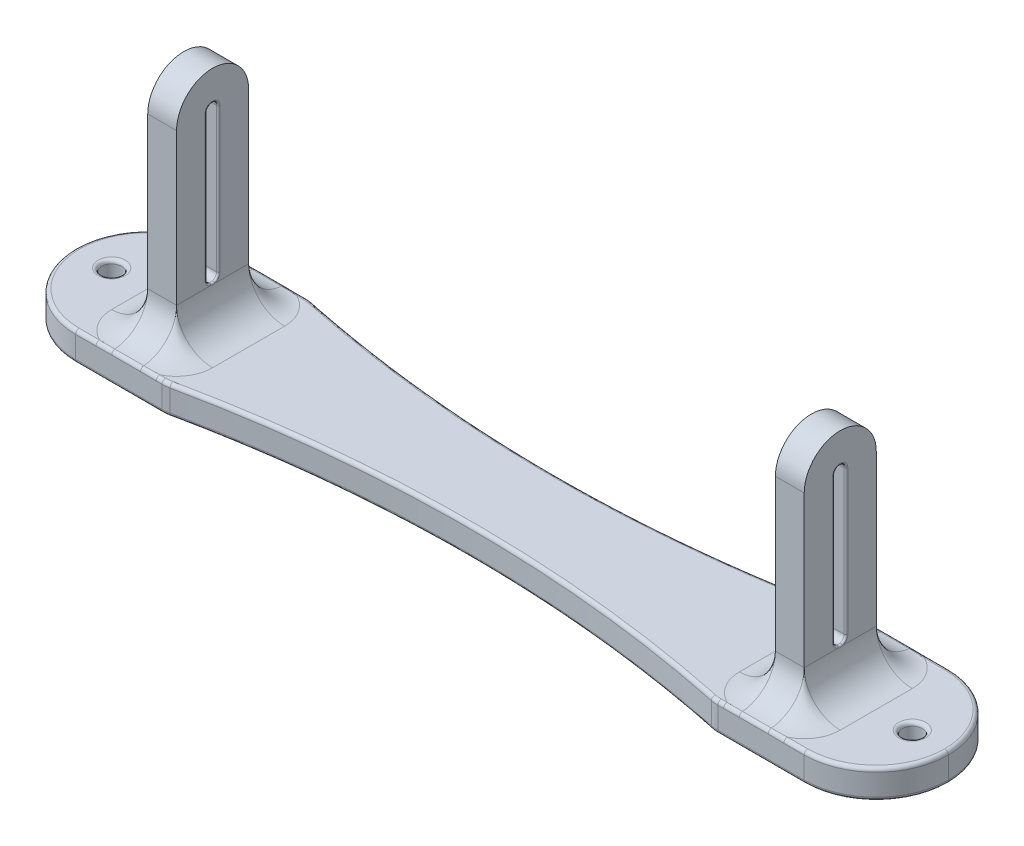
SolidWorks part; units mm, degrees
ref_plane "Front Plane" through (0, 0, 0) normal (0, 0, 1) x (1, 0, 0)
ref_plane "Top Plane" through (0, 0, 0) normal (0, 1, 0) x (1, 0, 0)
ref_plane "Right Plane" through (0, 0, 0) normal (1, 0, 0) x (0, 0, -1)
sketch "Sketch1" plane through (0, 0, 0) normal (0, 0, 1) x (1, 0, 0)
  line L1 (-91.1, 8) -> (-91.1, 70)
  line L2 (-91.1, 70) -> (-83.1, 70)
  line L3 (-83.1, 70) -> (-83.1, 8)
  line L5 (0, 0) -> (0, 8) construction
  line L10 (-121.1, 0) -> (-121.1, 8)
  line L11 (-121.1, 8) -> (-91.1, 8)
  line L12 (121.1, 0) -> (-121.1, 0)
  line L13 (83.1, 8) -> (-83.1, 8)
  line L14 (121.1, 8) -> (91.1, 8)
  line L15 (121.1, 0) -> (121.1, 8)
  line L16 (83.1, 70) -> (83.1, 8)
  line L17 (91.1, 70) -> (83.1, 70)
  line L18 (91.1, 8) -> (91.1, 70)
  dimension "D1" = 166.2
  dimension "D2" = 8
  dimension "D3" = 8
  dimension "D4" = 30
  dimension "D5" = 70
extrude "Boss-Extrude1" add sketch "Sketch1" along normal blind 40
sketch "Sketch2" plane through (91.1, 0, 0) normal (1, 0, 0) x (0, 0, -1)
  line L0 (-20, 60) -> (-20, 20) construction
  line L1 (-18.4, 60) -> (-18.4, 20)
  line L2 (-21.6, 60) -> (-21.6, 20)
  line L3 (-40, 70) -> (0, 70) construction
  arc A0 (-18.4, 60) -> (-21.6, 60) centre (-20, 60) ccw
  arc A1 (-21.6, 20) -> (-18.4, 20) centre (-20, 20) ccw
  point P2 (-20, 40)
  point P10 (-20, 70)
  dimension "D1" = 3.2
  dimension "D2" = 10
  dimension "D3" = 40
extrude "Cut-Extrude1" cut sketch "Sketch2" against normal through all
sketch "Sketch3" plane through (0, 8, 0) normal (0, 1, 0) x (1, 0, 0)
  line L0 (0, 0) -> (0, -40) construction
  line L1 (83.1, -40) -> (-83.1, -40) construction
  line L2 (-121.1, -40) -> (-121.1, 0) construction
  circle A0 centre (-111.1, -20) radius 2.75
  circle A1 centre (111.1, -20) radius 2.75
  point P9 (-121.1, -20)
  dimension "D1" = 5.5
  dimension "D2" = 10
extrude "Cut-Extrude2" cut sketch "Sketch3" against normal through all
sketch "Sketch4" plane through (91.1, 0, 0) normal (1, 0, 0) x (0, 0, -1)
  line L0 (-30, 8) -> (-30, 60)
  line L1 (-40, 8) -> (0, 8) construction
  line L2 (-10, 60) -> (-10, 8)
  line L3 (-10, 8) -> (-30, 8)
  line L4 (-40, 70) -> (0, 70) construction
  line L5 (-30, 8) -> (-46.3122, 8)
  line L6 (-46.3122, 8) -> (-46.3122, 72.7223)
  line L7 (-46.3122, 72.7223) -> (5.6666, 72.7223)
  line L8 (5.6666, 72.7223) -> (5.6666, 8)
  line L9 (5.6666, 8) -> (-10, 8)
  arc A0 (-30, 60) -> (-10, 60) centre (-20, 60) cw
  point P9 (-20, 70)
  point P10 (-20, 8)
  line M9 (0, 8) -> (0, 70)
  line M10 (0, 70) -> (-40, 70)
  line M11 (-40, 70) -> (-40, 8)
  line M12 (-40, 8) -> (0, 8)
  dimension "D1" = 20
extrude "Cut-Extrude3" cut sketch "Sketch4" against normal through all contours L9 L8 L7 L6 L5 M11 M10 M9 | L0 A0 M10 M11 M12 | A0 L2 M10 M12 M9 region at (91.1, 39.9624, 34.758) region at (91.1, 39.9624, 5.242) region at (91.1, 8.8301, 43.1561)
fillet "Fillet1" radius 20 4 edges at (-121.1, 4, 40) (-121.1, 4, 0) (121.1, 4, 40) (121.1, 4, 0)
fillet "Fillet2" radius 10 8 edges at (-87.1, 8, 30) (-91.1, 8, 20) (-83.1, 8, 20) (-87.1, 8, 10) (87.1, 8, 30) (91.1, 8, 20) (87.1, 8, 10) (83.1, 8, 20)
sketch "Sketch5" plane through (0, 8, 0) normal (0, 1, 0) x (1, 0, 0)
  line L0 (83.1, 0) -> (-83.1, 0) construction
  line L1 (-111.1, -20) -> (111.1, -20) construction
  line L2 (-76.1, 0) -> (76.1, 0)
  line L3 (76.1, -40) -> (-76.1, -40)
  circle A0 centre (-111.1, -20) radius 2.75 construction
  circle A1 centre (111.1, -20) radius 2.75 construction
  spline S0 degree 2 poles (-76.1, 0) (0, -16) (76.1, 0) knots 0 0 0 1 1 1
  spline S1 degree 2 poles (-76.1, -40) (0, -24) (76.1, -40) knots 0 0 0 1 1 1
  dimension "D1" = 35
  dimension "D2" = 35
  dimension "D3" = 8
extrude "Cut-Extrude4" cut sketch "Sketch5" against normal through all
fillet "Fillet3" radius 10 4 edges at (-76.1, 4, 40) (-76.1, 4, 0) (76.1, 4, 40) (76.1, 4, 0)
fillet "Fillet4" radius 1 22 edges at (-115.2421, 8, 5.8579) (-96.1, 8, 0) (-87.1, 8, 0) (-80.1166, 8, 0) (-76.112, 8, 0.0523) (76.112, 8, 0.0523) (80.1166, 8, 0) (87.1, 8, 0) (96.1, 8, 0) (115.2421, 8, 5.8579) (115.2421, 8, 34.1421) (96.1, 8, 40) (87.1, 8, 40) (80.1166, 8, 40) (76.112, 8, 39.9477) (-76.112, 8, 39.9477) (-80.1166, 8, 40) (-87.1, 8, 40) (-96.1, 8, 40) (-115.2421, 8, 34.1421)
fillet "Fillet5" radius 1 2 edges at (111.1, 8, 17.25) (-111.1, 8, 22.75)
fillet "Fillet6" radius 0.5 16 edges at (83.1, 18.4, 20) (83.1, 40, 21.6) (83.1, 61.6, 20) (91.1, 18.4, 20) (91.1, 40, 21.6) (91.1, 61.6, 20) (-83.1, 61.6, 20) (-83.1, 40, 21.6) (-83.1, 18.4, 20) (-91.1, 18.4, 20) (-91.1, 40, 21.6) (-91.1, 61.6, 20) (83.1, 40, 18.4) (91.1, 40, 18.4) (-83.1, 40, 18.4) (-91.1, 40, 18.4)
fillet "Fillet7" radius 1 14 edges at (-76.112, 0, 0.0523) (-89.1166, 0, 0) (-115.2421, 0, 5.8579) (-115.2421, 0, 34.1421) (-89.1166, 0, 40) (-76.112, 0, 39.9477) (76.112, 0, 39.9477) (89.1166, 0, 40) (115.2421, 0, 34.1421) (115.2421, 0, 5.8579) (89.1166, 0, 0) (76.112, 0, 0.0523)
